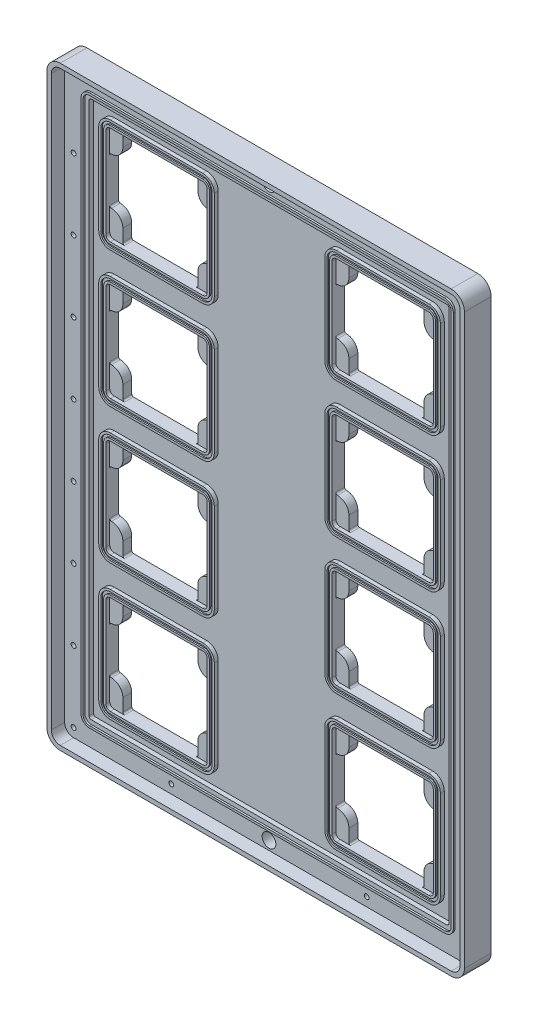
SolidWorks part; units mm, degrees
ref_plane "Front Plane" through (0, 0, 0) normal (0, 0, 1) x (1, 0, 0)
ref_plane "Top Plane" through (0, 0, 0) normal (0, 1, 0) x (1, 0, 0)
ref_plane "Right Plane" through (0, 0, 0) normal (1, 0, 0) x (0, 0, -1)
sketch "Sketch1" plane through (0, 0, 0) normal (0, 0, 1) x (1, 0, 0)
  line L1 (0, 0) -> (292.1, 0)
  line L2 (0, 0) -> (0, 419.1)
  line L3 (0, 419.1) -> (292.1, 419.1)
  line L4 (292.1, 0) -> (292.1, 419.1)
  dimension "D1" = 419.1
  dimension "D2" = 292.1
extrude "Boss-Extrude1" add sketch "Sketch1" along normal blind 9.525
sketch "Sketch4" plane through (0, 0, 9.525) normal (0, 0, 1) x (1, 0, 0)
  line L3 (0, 419.1) -> (0, 0) construction
  line L4 (6.35, 412.75) -> (285.75, 412.75) construction
  line L5 (6.35, 412.75) -> (6.35, 6.35) construction
  line L6 (6.35, 6.35) -> (285.75, 6.35) construction
  line L7 (285.75, 412.75) -> (285.75, 6.35) construction
  line L8 (292.1, 419.1) -> (0, 419.1) construction
  line L9 (292.1, 0) -> (292.1, 419.1) construction
  line L10 (0, 0) -> (292.1, 0) construction
  circle A0 centre (6.35, 6.35) radius 1.7272
  circle A1 centre (6.35, 412.75) radius 1.7272
  circle A2 centre (285.75, 412.75) radius 1.7272
  circle A3 centre (285.75, 6.35) radius 1.7272
  dimension "D5" = 3.4544
  dimension "D1" = 6.35
  dimension "D2" = 6.35
  dimension "D3" = 6.35
  dimension "D4" = 6.35
extrude "Cut-Extrude1" cut sketch "Sketch4" against normal blind 6.985
pattern_linear "LPattern2" count 8 spacing 50.8 along (0, -1, 0) of "Cut-Extrude1"
pattern_linear "LPattern3" count 4 spacing 69.85 along (-1, 0, 0) of "Cut-Extrude1"
sketch "Sketch5" plane through (0, 0, 9.525) normal (0, 0, 1) x (1, 0, 0)
  line L0 (0, 419.1) -> (0, 0) construction
  line L1 (19.05, 406.4) -> (273.05, 406.4) construction
  line L2 (12.7, 400.05) -> (12.7, 19.05) construction
  line L3 (19.05, 12.7) -> (273.05, 12.7) construction
  line L4 (279.4, 400.05) -> (279.4, 19.05) construction
  line L5 (292.1, 419.1) -> (0, 419.1) construction
  line L6 (292.1, 0) -> (292.1, 419.1) construction
  line L7 (0, 0) -> (292.1, 0) construction
  line L8 (19.05, 14.732) -> (273.05, 14.732) construction
  line L9 (14.732, 400.05) -> (14.732, 19.05) construction
  line L10 (19.05, 404.368) -> (273.05, 404.368) construction
  line L11 (277.368, 400.05) -> (277.368, 19.05) construction
  line L12 (12.954, 400.05) -> (12.954, 19.05)
  line L13 (19.05, 406.146) -> (273.05, 406.146)
  line L14 (279.146, 400.05) -> (279.146, 19.05)
  line L15 (19.05, 12.954) -> (273.05, 12.954)
  line L16 (277.622, 400.05) -> (277.622, 19.05)
  line L17 (19.05, 404.622) -> (273.05, 404.622)
  line L18 (14.478, 400.05) -> (14.478, 19.05)
  line L19 (19.05, 14.478) -> (273.05, 14.478)
  arc A0 (273.05, 12.7) -> (279.4, 19.05) centre (273.05, 19.05) ccw construction
  arc A1 (12.7, 19.05) -> (19.05, 12.7) centre (19.05, 19.05) ccw construction
  arc A2 (273.05, 406.4) -> (279.4, 400.05) centre (273.05, 400.05) cw construction
  arc A3 (19.05, 406.4) -> (12.7, 400.05) centre (19.05, 400.05) ccw construction
  arc A4 (14.732, 19.05) -> (19.05, 14.732) centre (19.05, 19.05) ccw construction
  arc A5 (19.05, 404.368) -> (14.732, 400.05) centre (19.05, 400.05) ccw construction
  arc A6 (273.05, 404.368) -> (277.368, 400.05) centre (273.05, 400.05) cw construction
  arc A7 (273.05, 14.732) -> (277.368, 19.05) centre (273.05, 19.05) ccw construction
  arc A8 (19.05, 406.146) -> (12.954, 400.05) centre (19.05, 400.05) ccw
  arc A9 (273.05, 406.146) -> (279.146, 400.05) centre (273.05, 400.05) cw
  arc A10 (273.05, 12.954) -> (279.146, 19.05) centre (273.05, 19.05) ccw
  arc A11 (12.954, 19.05) -> (19.05, 12.954) centre (19.05, 19.05) ccw
  arc A12 (273.05, 404.622) -> (277.622, 400.05) centre (273.05, 400.05) cw
  arc A13 (19.05, 404.622) -> (14.478, 400.05) centre (19.05, 400.05) ccw
  arc A14 (14.478, 19.05) -> (19.05, 14.478) centre (19.05, 19.05) ccw
  arc A15 (273.05, 14.478) -> (277.622, 19.05) centre (273.05, 19.05) ccw
  dimension "D5" = 6.35
  dimension "D1" = 12.7
  dimension "D2" = 12.7
  dimension "D3" = 12.7
  dimension "D4" = 12.7
  dimension "D6" = 2.032
  dimension "D7" = 2.032
  dimension "D8" = 0.254
  dimension "D9" = 0.254
  dimension "D10" = 0.254
sketch "Sketch6" plane through (0, 0, 9.525) normal (0, 0, 1) x (1, 0, 0)
  line L0 (292.1, 419.1) -> (0, 419.1) construction
  line L1 (0, 419.1) -> (0, 0) construction
  line L24 (273.05, 401.6375) -> (19.05, 401.6375)
  line L25 (274.6375, 19.05) -> (274.6375, 400.05)
  line L26 (19.05, 17.4625) -> (273.05, 17.4625)
  line L27 (17.4625, 400.05) -> (17.4625, 19.05)
  line L28 (273.05, 401.6375) -> (19.05, 401.6375)
  line L29 (274.6375, 19.05) -> (274.6375, 400.05)
  line L30 (19.05, 17.4625) -> (273.05, 17.4625)
  line L31 (17.4625, 400.05) -> (17.4625, 19.05)
  arc A20 (19.05, 401.6375) -> (17.4625, 400.05) centre (19.05, 400.05) ccw
  arc A21 (274.6375, 400.05) -> (273.05, 401.6375) centre (273.05, 400.05) ccw
  arc A22 (273.05, 17.4625) -> (274.6375, 19.05) centre (273.05, 19.05) ccw
  arc A23 (17.4625, 19.05) -> (19.05, 17.4625) centre (19.05, 19.05) ccw
  arc A24 (19.05, 401.6375) -> (17.4625, 400.05) centre (19.05, 400.05) ccw
  arc A25 (274.6375, 400.05) -> (273.05, 401.6375) centre (273.05, 400.05) ccw
  arc A26 (273.05, 17.4625) -> (274.6375, 19.05) centre (273.05, 19.05) ccw
  arc A27 (17.4625, 19.05) -> (19.05, 17.4625) centre (19.05, 19.05) ccw
  dimension "D2" = 17.4625
  dimension "D3" = 17.4625
  dimension "D1" = 2.7305
extrude "Cut-Extrude3" cut sketch "Sketch6" against normal blind 3.175
extrude "Boss-Extrude2" add sketch "Sketch5" along normal blind 1.3335 contours L12 A11 L15 A10 L14 A9 L13 A8 A15 L19 A14 L18 A13 L17 A12 L16 region at (15.0752, 404.0248, 9.525)
sketch "Sketch7" plane through (0, 0, 9.525) normal (0, 0, 1) x (1, 0, 0)
  circle A0 centre (146.05, 6.35) radius 4.9022
  circle A1 centre (146.05, 412.75) radius 4.9022
  dimension "D1" = 9.8044
extrude "Cut-Extrude4" cut sketch "Sketch7" against normal through all
fillet "Fillet1" radius 6.35 4 edges at (0, 419.1, 4.7625) (292.1, 419.1, 4.7625) (0, 0, 4.7625) (292.1, 0, 4.7625)
sketch "Sketch8" plane through (0, 0, 0) normal (0, 0, -1) x (-1, 0, 0)
  line L0 (-264.668, 370.459) -> (-264.668, 339.2678)
  line L1 (-255.27, 329.8698) -> (-255.27, 320.8782)
  line L2 (-252.4506, 318.0588) -> (-201.2442, 318.0588)
  line L3 (-198.4248, 320.8782) -> (-198.4248, 329.8698)
  line L4 (-189.0268, 339.2678) -> (-189.0268, 370.459)
  line L5 (-198.4248, 379.857) -> (-198.4248, 388.8486)
  line L6 (-201.2442, 391.668) -> (-252.4506, 391.668)
  line L7 (-255.27, 388.8486) -> (-255.27, 379.857)
  line L8 (-261.8486, 391.668) -> (-261.8486, 318.0588) construction
  line L9 (-264.668, 388.8486) -> (-189.0268, 388.8486) construction
  line L10 (-264.668, 391.668) -> (-189.0268, 391.668) construction
  line L11 (-264.668, 391.668) -> (-264.668, 318.0588) construction
  line L12 (-264.668, 318.0588) -> (-189.0268, 318.0588) construction
  line L13 (-189.0268, 391.668) -> (-189.0268, 318.0588) construction
  line L14 (-264.668, 379.857) -> (-189.0268, 379.857) construction
  line L15 (-264.668, 370.459) -> (-189.0268, 370.459) construction
  line L16 (-264.668, 339.2678) -> (-189.0268, 339.2678) construction
  line L17 (-264.668, 329.8698) -> (-189.0268, 329.8698) construction
  line L18 (-264.668, 320.8782) -> (-189.0268, 320.8782) construction
  line L19 (-255.27, 318.0588) -> (-255.27, 391.668) construction
  line L20 (-252.4506, 391.668) -> (-252.4506, 318.0588) construction
  line L21 (-201.2442, 391.668) -> (-201.2442, 318.0588) construction
  line L22 (-198.4248, 391.668) -> (-198.4248, 318.0588) construction
  line L23 (-191.8462, 318.0588) -> (-191.8462, 391.668) construction
  line L24 (-189.0268, 373.2784) -> (-264.668, 373.2784) construction
  line L27 (-201.2442, 393.7) -> (-252.4506, 393.7)
  line L28 (-257.302, 388.8486) -> (-257.302, 379.857)
  line L29 (-266.7, 370.459) -> (-266.7, 339.2678)
  line L30 (-257.302, 329.8698) -> (-257.302, 320.8782)
  line L31 (-252.4506, 316.0268) -> (-201.2442, 316.0268)
  line L32 (-196.3928, 320.8782) -> (-196.3928, 329.8698)
  line L33 (-186.9948, 339.2678) -> (-186.9948, 370.459)
  line L34 (-196.3928, 379.857) -> (-196.3928, 388.8486)
  line L35 (-285.75, 419.1) -> (-6.35, 419.1) construction
  line L36 (-292.1, 6.35) -> (-292.1, 412.75) construction
  arc A0 (-261.8486, 373.2784) -> (-255.27, 379.857) centre (-261.8486, 379.857) ccw
  arc A1 (-261.8486, 373.2784) -> (-264.668, 370.459) centre (-261.8486, 370.459) ccw
  arc A2 (-264.668, 339.2678) -> (-261.8486, 336.4484) centre (-261.8486, 339.2678) ccw
  arc A3 (-255.27, 329.8698) -> (-261.8486, 336.4484) centre (-261.8486, 329.8698) ccw
  arc A4 (-255.27, 320.8782) -> (-252.4506, 318.0588) centre (-252.4506, 320.8782) ccw
  arc A5 (-201.2442, 318.0588) -> (-198.4248, 320.8782) centre (-201.2442, 320.8782) ccw
  arc A6 (-191.8462, 336.4484) -> (-198.4248, 329.8698) centre (-191.8462, 329.8698) ccw
  arc A7 (-191.8462, 336.4484) -> (-189.0268, 339.2678) centre (-191.8462, 339.2678) ccw
  arc A8 (-189.0268, 370.459) -> (-191.8462, 373.2784) centre (-191.8462, 370.459) ccw
  arc A9 (-198.4248, 379.857) -> (-191.8462, 373.2784) centre (-191.8462, 379.857) ccw
  arc A10 (-198.4248, 388.8486) -> (-201.2442, 391.668) centre (-201.2442, 388.8486) ccw
  arc A11 (-252.4506, 391.668) -> (-255.27, 388.8486) centre (-252.4506, 388.8486) ccw
  arc A12 (-252.4506, 393.7) -> (-257.302, 388.8486) centre (-252.4506, 388.8486) ccw
  arc A13 (-261.8486, 375.3104) -> (-257.302, 379.857) centre (-261.8486, 379.857) ccw
  arc A14 (-261.8486, 375.3104) -> (-266.7, 370.459) centre (-261.8486, 370.459) ccw
  arc A15 (-266.7, 339.2678) -> (-261.8486, 334.4164) centre (-261.8486, 339.2678) ccw
  arc A16 (-257.302, 329.8698) -> (-261.8486, 334.4164) centre (-261.8486, 329.8698) ccw
  arc A17 (-257.302, 320.8782) -> (-252.4506, 316.0268) centre (-252.4506, 320.8782) ccw
  arc A18 (-201.2442, 316.0268) -> (-196.3928, 320.8782) centre (-201.2442, 320.8782) ccw
  arc A19 (-191.8462, 334.4164) -> (-196.3928, 329.8698) centre (-191.8462, 329.8698) ccw
  arc A20 (-191.8462, 334.4164) -> (-186.9948, 339.2678) centre (-191.8462, 339.2678) ccw
  arc A21 (-186.9948, 370.459) -> (-191.8462, 375.3104) centre (-191.8462, 370.459) ccw
  arc A22 (-196.3928, 379.857) -> (-191.8462, 375.3104) centre (-191.8462, 379.857) ccw
  arc A23 (-196.3928, 388.8486) -> (-201.2442, 393.7) centre (-201.2442, 388.8486) ccw
  dimension "D4" = 11.811
  dimension "D5" = 21.209
  dimension "D6" = 52.4002
  dimension "D1" = 73.6092
  dimension "D2" = 75.6412
  dimension "D3" = 2.8194
  dimension "D7" = 61.7982
  dimension "D8" = 70.7898
  dimension "D9" = 2.8194
  dimension "D10" = 9.398
  dimension "D11" = 12.2174
  dimension "D12" = 63.4238
  dimension "D13" = 66.2432
  dimension "D14" = 72.8218
  dimension "D15" = 55.2196
  dimension "D16" = 25.4
  dimension "D17" = 25.4
  dimension "D18" = 2.032
extrude "Cut-Extrude5" cut sketch "Sketch8" against normal blind 3.175
sketch "Sketch10" plane through (0, 0, 0) normal (0, 0, -1) x (-1, 0, 0)
  line L18 (-263.0805, 370.459) -> (-263.0805, 339.2678)
  line L19 (-253.6825, 329.8698) -> (-253.6825, 320.8782)
  line L20 (-252.4506, 319.6463) -> (-201.2442, 319.6463)
  line L21 (-200.0123, 320.8782) -> (-200.0123, 329.8698)
  line L22 (-190.6143, 339.2678) -> (-190.6143, 370.459)
  line L23 (-200.0123, 379.857) -> (-200.0123, 388.8486)
  line L24 (-201.2442, 390.0805) -> (-252.4506, 390.0805)
  line L25 (-253.6825, 388.8486) -> (-253.6825, 379.857)
  line L26 (-263.0805, 370.459) -> (-263.0805, 339.2678)
  line L27 (-253.6825, 329.8698) -> (-253.6825, 320.8782)
  line L28 (-252.4506, 319.6463) -> (-201.2442, 319.6463)
  line L29 (-200.0123, 320.8782) -> (-200.0123, 329.8698)
  line L30 (-190.6143, 339.2678) -> (-190.6143, 370.459)
  line L31 (-200.0123, 379.857) -> (-200.0123, 388.8486)
  line L32 (-201.2442, 390.0805) -> (-252.4506, 390.0805)
  line L33 (-253.6825, 388.8486) -> (-253.6825, 379.857)
  arc A28 (-261.8486, 371.6909) -> (-263.0805, 370.459) centre (-261.8486, 370.459) ccw
  arc A29 (-263.0805, 339.2678) -> (-261.8486, 338.0359) centre (-261.8486, 339.2678) ccw
  arc A30 (-253.6825, 329.8698) -> (-261.8486, 338.0359) centre (-261.8486, 329.8698) ccw
  arc A31 (-253.6825, 320.8782) -> (-252.4506, 319.6463) centre (-252.4506, 320.8782) ccw
  arc A32 (-201.2442, 319.6463) -> (-200.0123, 320.8782) centre (-201.2442, 320.8782) ccw
  arc A33 (-191.8462, 338.0359) -> (-200.0123, 329.8698) centre (-191.8462, 329.8698) ccw
  arc A34 (-191.8462, 338.0359) -> (-190.6143, 339.2678) centre (-191.8462, 339.2678) ccw
  arc A35 (-190.6143, 370.459) -> (-191.8462, 371.6909) centre (-191.8462, 370.459) ccw
  arc A36 (-200.0123, 379.857) -> (-191.8462, 371.6909) centre (-191.8462, 379.857) ccw
  arc A37 (-200.0123, 388.8486) -> (-201.2442, 390.0805) centre (-201.2442, 388.8486) ccw
  arc A38 (-252.4506, 390.0805) -> (-253.6825, 388.8486) centre (-252.4506, 388.8486) ccw
  arc A39 (-261.8486, 371.6909) -> (-253.6825, 379.857) centre (-261.8486, 379.857) ccw
  arc A40 (-261.8486, 371.6909) -> (-263.0805, 370.459) centre (-261.8486, 370.459) ccw
  arc A41 (-263.0805, 339.2678) -> (-261.8486, 338.0359) centre (-261.8486, 339.2678) ccw
  arc A42 (-253.6825, 329.8698) -> (-261.8486, 338.0359) centre (-261.8486, 329.8698) ccw
  arc A43 (-253.6825, 320.8782) -> (-252.4506, 319.6463) centre (-252.4506, 320.8782) ccw
  arc A44 (-201.2442, 319.6463) -> (-200.0123, 320.8782) centre (-201.2442, 320.8782) ccw
  arc A45 (-191.8462, 338.0359) -> (-200.0123, 329.8698) centre (-191.8462, 329.8698) ccw
  arc A46 (-191.8462, 338.0359) -> (-190.6143, 339.2678) centre (-191.8462, 339.2678) ccw
  arc A47 (-190.6143, 370.459) -> (-191.8462, 371.6909) centre (-191.8462, 370.459) ccw
  arc A48 (-200.0123, 379.857) -> (-191.8462, 371.6909) centre (-191.8462, 379.857) ccw
  arc A49 (-200.0123, 388.8486) -> (-201.2442, 390.0805) centre (-201.2442, 388.8486) ccw
  arc A50 (-252.4506, 390.0805) -> (-253.6825, 388.8486) centre (-252.4506, 388.8486) ccw
  arc A51 (-261.8486, 371.6909) -> (-253.6825, 379.857) centre (-261.8486, 379.857) ccw
  dimension "D1" = 1.5875
extrude "Cut-Extrude6" cut sketch "Sketch10" against normal through all
sketch "Sketch11" plane through (0, 0, 0) normal (0, 0, -1) x (-1, 0, 0)
  line L0 (-226.8474, 388.8994) -> (-226.8474, 393.7) construction
  line L1 (-261.8486, 388.8994) -> (-191.8462, 388.8994) construction
  line L2 (-261.8486, 388.8994) -> (-261.8486, 320.8274) construction
  line L3 (-261.8486, 320.8274) -> (-191.8462, 320.8274) construction
  line L4 (-191.8462, 388.8994) -> (-191.8462, 320.8274) construction
  line L5 (-201.2442, 393.7) -> (-252.4506, 393.7) construction
  line L6 (-226.8474, 320.8274) -> (-226.8474, 316.0268) construction
  line L7 (-252.4506, 316.0268) -> (-201.2442, 316.0268) construction
  line L8 (-261.8486, 354.8634) -> (-266.7, 354.8634) construction
  line L9 (-266.7, 370.459) -> (-266.7, 339.2678) construction
  line L10 (-191.8462, 354.8634) -> (-186.9948, 354.8634) construction
  line L11 (-186.9948, 339.2678) -> (-186.9948, 370.459) construction
  circle A0 centre (-261.8486, 388.8994) radius 1.1303
  circle A1 centre (-191.8462, 388.8994) radius 1.1303
  circle A2 centre (-191.8462, 320.8274) radius 1.1303
  circle A3 centre (-261.8486, 320.8274) radius 1.1303
  dimension "D3" = 2.2606
  dimension "D1" = 70.0024
  dimension "D2" = 68.072
extrude "Cut-Extrude7" cut sketch "Sketch11" against normal blind 3.9688
sketch "Sketch12" plane through (0, 0, 6.35) normal (0, 0, 1) x (1, 0, 0)
  line L0 (252.4506, 390.0805) -> (201.2442, 390.0805) construction
  line L1 (193.7893, 390.0805) -> (259.9055, 390.0805)
  line L2 (190.6143, 386.9055) -> (190.6143, 322.8213)
  line L3 (193.7893, 319.6463) -> (259.9055, 319.6463)
  line L4 (263.0805, 386.9055) -> (263.0805, 322.8213)
  line L5 (263.0805, 339.2678) -> (263.0805, 370.459) construction
  line L10 (193.7893, 391.668) -> (259.9055, 391.668)
  line L11 (264.668, 386.9055) -> (264.668, 322.8213)
  line L12 (193.7893, 318.0588) -> (259.9055, 318.0588)
  line L13 (189.0268, 386.9055) -> (189.0268, 322.8213)
  line L14 (187.1218, 386.9055) -> (187.1218, 322.8213)
  line L15 (193.7893, 316.1538) -> (259.9055, 316.1538)
  line L16 (266.573, 386.9055) -> (266.573, 322.8213)
  line L17 (193.7893, 393.573) -> (259.9055, 393.573)
  line L18 (185.5343, 386.9055) -> (185.5343, 322.8213)
  line L19 (193.7893, 314.5663) -> (259.9055, 314.5663)
  line L20 (268.1605, 386.9055) -> (268.1605, 322.8213)
  line L21 (193.7893, 395.1605) -> (259.9055, 395.1605)
  line L22 (201.2442, 319.6463) -> (252.4506, 319.6463) construction
  line L23 (190.6143, 370.459) -> (190.6143, 339.2678) construction
  arc A0 (259.9055, 319.6463) -> (263.0805, 322.8213) centre (259.9055, 322.8213) ccw
  arc A1 (190.6143, 322.8213) -> (193.7893, 319.6463) centre (193.7893, 322.8213) ccw
  arc A2 (259.9055, 390.0805) -> (263.0805, 386.9055) centre (259.9055, 386.9055) cw
  arc A3 (193.7893, 390.0805) -> (190.6143, 386.9055) centre (193.7893, 386.9055) ccw
  arc A4 (259.9055, 391.668) -> (264.668, 386.9055) centre (259.9055, 386.9055) cw
  arc A5 (259.9055, 318.0588) -> (264.668, 322.8213) centre (259.9055, 322.8213) ccw
  arc A6 (189.0268, 322.8213) -> (193.7893, 318.0588) centre (193.7893, 322.8213) ccw
  arc A7 (193.7893, 391.668) -> (189.0268, 386.9055) centre (193.7893, 386.9055) ccw
  arc A8 (187.1218, 322.8213) -> (193.7893, 316.1538) centre (193.7893, 322.8213) ccw
  arc A9 (259.9055, 316.1538) -> (266.573, 322.8213) centre (259.9055, 322.8213) ccw
  arc A10 (259.9055, 393.573) -> (266.573, 386.9055) centre (259.9055, 386.9055) cw
  arc A11 (193.7893, 393.573) -> (187.1218, 386.9055) centre (193.7893, 386.9055) ccw
  arc A12 (185.5343, 322.8213) -> (193.7893, 314.5663) centre (193.7893, 322.8213) ccw
  arc A13 (259.9055, 314.5663) -> (268.1605, 322.8213) centre (259.9055, 322.8213) ccw
  arc A14 (259.9055, 395.1605) -> (268.1605, 386.9055) centre (259.9055, 386.9055) cw
  arc A15 (193.7893, 395.1605) -> (185.5343, 386.9055) centre (193.7893, 386.9055) ccw
  dimension "D1" = 3.175
  dimension "D2" = 1.5875
  dimension "D3" = 1.905
  dimension "D4" = 1.5875
extrude "Boss-Extrude3" add sketch "Sketch12" along normal blind 2.794 contours L21 A15 L18 A12 L19 A13 L20 A14 A11 L17 A10 L16 A9 L15 A8 L14 | L10 A7 L13 A6 L12 A5 L11 A4 A3 L1 A2 L4 A0 L3 A1 L2 region at (226.8474, 390.6125, 6.35) region at (188.7683, 391.9265, 6.35)
extrude "Boss-Extrude4" add sketch "Sketch12<3>" along normal blind 1.778 contours L17 A11 L14 A8 L15 A9 L16 A10 A7 L10 A4 L11 A5 L12 A6 L13 region at (189.8591, 390.8357, 6.35)
sketch "Sketch12<3>" plane through (0, 0, 6.35) normal (0, 0, 1) x (1, 0, 0) same geometry as "Sketch12"
pattern_linear "LPattern1" count 2 spacing 161.5948 along (-1, 0, 0) count 4 spacing 96.8756 along (0, -1, 0) of "Cut-Extrude6", "Cut-Extrude5", "Cut-Extrude7", "Boss-Extrude3", "Boss-Extrude4"
sketch "Sketch13" plane through (0, 0, 0) normal (0, 0, -1) x (-1, 0, 0)
  line L4 (-6.35, 419.1) -> (-285.75, 419.1)
  line L5 (-292.1, 412.75) -> (-292.1, 6.35)
  line L6 (-285.75, 0) -> (-6.35, 0)
  line L7 (0, 6.35) -> (0, 412.75)
  line L8 (-285.75, -3.175) -> (-6.35, -3.175)
  line L9 (3.175, 6.35) -> (3.175, 412.75)
  line L10 (-6.35, 422.275) -> (-285.75, 422.275)
  line L11 (-295.275, 412.75) -> (-295.275, 6.35)
  line L12 (-285.75, -3.175) -> (-6.35, -3.175)
  line L13 (3.175, 6.35) -> (3.175, 412.75)
  line L14 (-6.35, 422.275) -> (-285.75, 422.275)
  line L15 (-295.275, 412.75) -> (-295.275, 6.35)
  arc A4 (-285.75, 419.1) -> (-292.1, 412.75) centre (-285.75, 412.75) ccw
  arc A5 (-292.1, 6.35) -> (-285.75, 0) centre (-285.75, 6.35) ccw
  arc A6 (-6.35, 0) -> (0, 6.35) centre (-6.35, 6.35) ccw
  arc A7 (0, 412.75) -> (-6.35, 419.1) centre (-6.35, 412.75) ccw
  arc A8 (-295.275, 6.35) -> (-285.75, -3.175) centre (-285.75, 6.35) ccw
  arc A9 (-6.35, -3.175) -> (3.175, 6.35) centre (-6.35, 6.35) ccw
  arc A10 (3.175, 412.75) -> (-6.35, 422.275) centre (-6.35, 412.75) ccw
  arc A11 (-285.75, 422.275) -> (-295.275, 412.75) centre (-285.75, 412.75) ccw
  arc A12 (-295.275, 6.35) -> (-285.75, -3.175) centre (-285.75, 6.35) ccw
  arc A13 (-6.35, -3.175) -> (3.175, 6.35) centre (-6.35, 6.35) ccw
  arc A14 (3.175, 412.75) -> (-6.35, 422.275) centre (-6.35, 412.75) ccw
  arc A15 (-285.75, 422.275) -> (-295.275, 412.75) centre (-285.75, 412.75) ccw
  dimension "D1" = 3.175
  dimension "D2" = 3.175
extrude "Boss-Extrude5" add sketch "Sketch13" against normal blind 19.05
